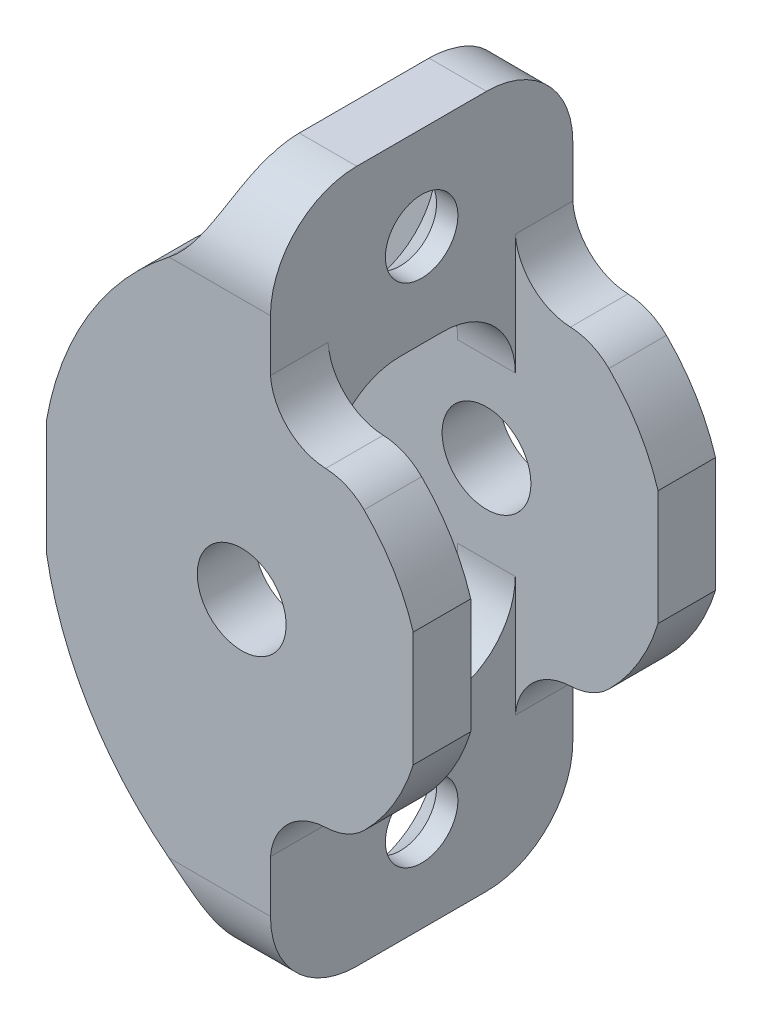
SolidWorks part; units mm, degrees
material "6061-T6 (SS)"
ref_plane "X-Y Datum" through (0, 0, 0) normal (0, 0, 1) x (1, 0, 0)
ref_plane "X-Z Datum" through (0, 0, 0) normal (0, 1, 0) x (1, 0, 0)
ref_plane "Y-Z Datum" through (0, 0, 0) normal (1, 0, 0) x (0, 0, -1)
sketch "Sketch2" plane through (0, 0, 0) normal (1, 0, 0) x (0, 0, -1)
  line L1 (0, 0) -> (33.3756, 0)
  line L2 (0, 0) -> (0, 76.487)
  line L3 (0, 76.487) -> (33.3756, 76.487)
  line L4 (33.3756, 0) -> (33.3756, 76.487)
  dimension "D1" = 33.3756
  dimension "D2" = 76.487
extrude "Body Extrude" add sketch "Sketch2" along normal mid plane 6.35
sketch "Sketch3" plane through (0, 0, 0) normal (0, 0, 1) x (1, 0, 0)
  line L1 (18.9361, 44.5935) -> (18.9361, 31.8935)
  line L2 (-21.5568, 44.5935) -> (-21.5568, 31.8935)
  line L5 (0, 0) -> (0, -50000) construction
  line L6 (3.175, 38.2435) -> (-21.5568, 38.2435) construction
  line L7 (3.175, 76.487) -> (3.175, 0) construction
  line L8 (-3.175, 76.487) -> (-3.175, 0) construction
  line L9 (-3.175, 6.35) -> (3.175, 14.224)
  line L10 (3.175, 0) -> (-3.175, 0) construction
  line L11 (-3.175, 70.137) -> (3.175, 62.263)
  arc A8 (3.175, 14.224) -> (9.271, 21.082) centre (9.5043, 14.7363) cw
  arc A9 (9.271, 21.082) -> (13.5113, 22.9211) centre (9.0377, 27.4277) ccw
  arc A10 (13.5113, 22.9211) -> (18.9361, 31.8935) centre (-1.699, 38.2435) ccw
  arc A11 (-3.175, 6.35) -> (-21.5568, 31.8935) centre (14.2058, 38.2435) cw
  arc A12 (9.271, 55.405) -> (13.5113, 53.5659) centre (9.0377, 49.0593) cw
  arc A13 (3.175, 62.263) -> (9.271, 55.405) centre (9.5043, 61.7507) ccw
  arc A14 (18.9361, 44.5935) -> (13.5113, 53.5659) centre (-1.699, 38.2435) ccw
  arc A15 (-21.5568, 44.5935) -> (-3.175, 70.137) centre (14.2058, 38.2435) cw
  point P3 (0, 0)
  point P6 (3.175, 38.2435)
  point P9 (-3.175, 38.2435)
  point P23 (13.5113, 53.5659)
  point P29 (-3.175, 70.137)
  dimension "D1" = 6.35
  dimension "D5" = 21.082
  dimension "D7" = 21.59
  dimension "D8" = 36.322
  dimension "D3" = 6.35
  dimension "D6" = 6.35
  dimension "D2" = 14.224
  dimension "D4" = 6.096
  dimension "D9" = 12.7
  dimension "D10" = 12.7
extrude "Round Extrude" add sketch "Sketch3" against normal blind 6.35
ref_plane "Plane1" through (0, 0, -16.6878) normal (0, 0, -1) x (-1, 0, 0)
mirror "Round Extrude Mirrored" about plane through (0, 0, -16.6878) normal (0, 0, -1) of "Round Extrude"
sketch "Sketch5" plane through (3.175, 0, 0) normal (1, 0, 0) x (0, 0, -1)
  line L0 (0, 38.2435) -> (-50000, 38.2435) construction
  line L1 (6.35, 55.405) -> (6.35, 61.2384) construction
  line L3 (16.6878, 76.487) -> (16.6878, 50076.487) construction
  line L4 (33.3756, 76.487) -> (0, 76.487) construction
  line L5 (6.35, 55.9092) -> (27.0256, 55.9092)
  line L6 (6.35, 55.9092) -> (6.35, 20.5778)
  line L7 (6.35, 20.5778) -> (27.0256, 20.5778)
  line L8 (27.0256, 55.9092) -> (27.0256, 20.5778)
  line L9 (27.0256, 21.082) -> (27.0256, 15.2486) construction
  line L10 (33.3756, 31.8935) -> (33.3756, 44.5935) construction
  line L11 (33.3756, 31.8935) -> (33.3756, 44.5935) construction
  point P9 (16.6878, 76.487)
  point P20 (33.3756, 38.2435)
  dimension "D1" = 35.3314
  dimension "D2" = 17.6657
extrude "Rectangle Cut" cut sketch "Sketch5" against normal through all
fillet "Back Edge Fillet" radius 12.7 4 edges at (-3.175, 6.35, -30.2006) (-3.175, 6.35, -3.175) (-3.175, 70.137, -30.2006) (-3.175, 70.137, -3.175)
fillet "Outer Fillet" radius 9.525 4 edges at (0, 0, -33.3756) (0, 0, 0) (0, 76.487, -33.3756) (0, 76.487, 0)
fillet "Inner Fillet" radius 7.9375 4 edges at (0, 55.9092, -27.0256) (0, 55.9092, -6.35) (0, 20.5778, -6.35) (0, 20.5778, -27.0256)
sketch "Hole Reference Sketch" plane through (0, 0, 0) normal (1, 0, 0) x (0, 0, -1)
  line L0 (0, 38.2435) -> (50000, 38.2435) construction
  line L2 (16.6878, 76.487) -> (16.6878, -49923.513) construction
  line L3 (23.8506, 76.487) -> (9.525, 76.487) construction
  line L4 (9.525, 0) -> (23.8506, 0) construction
  line L5 (33.3756, 31.8935) -> (33.3756, 44.5935) construction
  line L6 (33.3756, 31.8935) -> (33.3756, 44.5935) construction
  point P9 (16.6878, 76.487)
  point P10 (16.6878, 10.287)
  point P13 (16.6878, 66.2)
  point P16 (33.3756, 38.2435)
  dimension "D1" = 10.287
hole_wizard "CSK for M8 Cross Countersunk Head Screw1" positions "Sketch7" profile "Sketch8" countersink size "M8" standard "AS"
sketch "Sketch7" plane through (-3.175, 0, 0) normal (-1, 0, 0) x (0, 0, 1)
  point P0 (-16.6878, 66.2)
  point P3 (-16.6878, 10.287)
  point P6 (0, 0)
  point P7 (0, 0)
sketch "Sketch8" plane through (-3.175, 66.2, -16.6878) normal (0, 1, 0) x (0, 0, 1)
  line L0 (0, 0) -> (0, 33.782)
  line L1 (0, 33.782) -> (4, 33.782)
  line L2 (4, 33.782) -> (4, 4)
  line L3 (4, 4) -> (8, 0)
  line L5 (8, 0) -> (0, 0)
  line L6 (-4, 4) -> (-8, 0) construction
  line L10 (0, 33.782) -> (-4, 33.782) construction
  line L11 (0, -6.35) -> (0, 107.95) construction
  dimension "Hole Dia." = 8
  dimension "Hole Depth" = 33.782
  dimension "Near C'Sink Dia." = 16
  dimension "Near C'Sink Angle" = 90
  dimension "Drill Angle" = 180
sketch "Sketch9" plane through (0, 0, 0) normal (0, 0, 1) x (1, 0, 0)
  line L0 (0, 200076.487) -> (0, -249923.513) construction
  line L1 (-22.1162, 38.2435) -> (49977.8838, 38.2435) construction
  line L2 (-21.5568, 44.5935) -> (-21.5568, 31.8935) construction
  line L3 (-21.5568, 44.5935) -> (-21.5568, 31.8935) construction
  circle A0 centre (0, 38.2435) radius 4.9022
  point P12 (-21.5568, 38.2435)
  point P13 (-17.408, 98.054)
  point P14 (13.5067, 73.8389)
  dimension "D1" = 9.8044
extrude "Vertical Holes" cut sketch "Sketch9" against normal through all both and the other way through all
sketch "Side Contour Sketch" plane through (-3.175, 0, 0) normal (-1, 0, 0) x (0, 0, 1)
  line L3 (-33.3756, 9.5585) -> (-33.3756, 9.525) construction
  line L4 (-33.3756, 9.5585) -> (-33.3756, 9.525) construction
  line L5 (-9.525, 0) -> (-23.8506, 0) construction
  line L7 (-23.8506, 76.487) -> (-9.525, 76.487) construction
  line L11 (-33.3756, 9.5585) -> (-33.3756, 9.525)
  line L12 (-33.3756, 9.5585) -> (-33.3756, 9.525)
  line L13 (-9.525, 0) -> (-23.8506, 0)
  line L15 (-23.8506, 76.487) -> (-9.525, 76.487)
  line L16 (0, 9.5585) -> (0, 31.8935) construction
  line L17 (-33.3756, 9.5585) -> (-33.3756, 9.525)
  line L20 (0, 44.5935) -> (0, 31.8935) construction
  line L21 (0, 44.5935) -> (0, 66.9285) construction
  line L22 (-33.3756, 66.9285) -> (-33.3756, 44.5935) construction
  line L23 (-33.3756, 31.8935) -> (-33.3756, 44.5935) construction
  line L24 (-33.3756, 31.8935) -> (-33.3756, 9.5585) construction
  line L25 (0, 9.5585) -> (0, 31.8935)
  line L26 (0, 44.5935) -> (0, 31.8935)
  line L27 (0, 44.5935) -> (0, 66.9285)
  line L28 (-33.3756, 66.9285) -> (-33.3756, 44.5935)
  line L29 (-33.3756, 31.8935) -> (-33.3756, 44.5935)
  line L30 (-33.3756, 31.8935) -> (-33.3756, 9.5585)
  line L31 (0, 9.525) -> (0, 9.5585) construction
  line L32 (0, 9.525) -> (0, 9.5585)
  line L33 (-33.3756, 66.962) -> (-33.3756, 66.9285) construction
  line L34 (0, 66.9285) -> (0, 66.962) construction
  line L35 (-33.3756, 66.962) -> (-33.3756, 66.9285)
  line L36 (0, 66.9285) -> (0, 66.962)
  arc A0 (-6.35, 75.9423) -> (-9.525, 76.487) centre (-9.525, 66.962) ccw construction
  arc A2 (-6.35, 0.5447) -> (0, 9.525) centre (-9.525, 9.525) ccw construction
  arc A3 (-9.525, 0) -> (-6.35, 0.5447) centre (-9.525, 9.525) ccw construction
  arc A4 (-27.0256, 0.5447) -> (-23.8506, 0) centre (-23.8506, 9.525) ccw construction
  arc A5 (-33.3756, 9.525) -> (-27.0256, 0.5447) centre (-23.8506, 9.525) ccw construction
  arc A7 (-23.8506, 76.487) -> (-27.0256, 75.9423) centre (-23.8506, 66.962) ccw construction
  arc A8 (-6.35, 75.9423) -> (-9.525, 76.487) centre (-9.525, 66.962) ccw
  arc A10 (-6.35, 0.5447) -> (0, 9.525) centre (-9.525, 9.525) ccw
  arc A11 (-9.525, 0) -> (-6.35, 0.5447) centre (-9.525, 9.525) ccw
  arc A12 (-27.0256, 0.5447) -> (-23.8506, 0) centre (-23.8506, 9.525) ccw
  arc A13 (-33.3756, 9.525) -> (-27.0256, 0.5447) centre (-23.8506, 9.525) ccw
  arc A15 (-23.8506, 76.487) -> (-27.0256, 75.9423) centre (-23.8506, 66.962) ccw
  arc A20 (-27.0256, 75.9423) -> (-33.3756, 66.962) centre (-23.8506, 66.962) ccw construction
  arc A21 (0, 66.962) -> (-6.35, 75.9423) centre (-9.525, 66.962) ccw construction
  arc A22 (-27.0256, 75.9423) -> (-33.3756, 66.962) centre (-23.8506, 66.962) ccw
  arc A23 (0, 66.962) -> (-6.35, 75.9423) centre (-9.525, 66.962) ccw
sketch "Slot Sketch" plane through (-3.175, 0, 0) normal (-1, 0, 0) x (0, 0, 1)
  line L0 (-23.8506, 76.487) -> (-9.525, 76.487) construction
  line L1 (-27.0256, 0) -> (-6.35, 0)
  line L2 (-27.0256, 0) -> (-27.0256, 76.487)
  line L3 (-27.0256, 76.487) -> (-6.35, 76.487)
  line L4 (-6.35, 0) -> (-6.35, 76.487)
  line L7 (-27.0256, 47.9717) -> (-27.0256, 75.9423) construction
  dimension "D1" = 20.6756
  dimension "D2" = 76.487
sketch "Hole Contour" plane through (-3.175, 0, 0) normal (-1, 0, 0) x (0, 0, 1)
  line L0 (-27.0256, 0) -> (-27.0256, 76.487) construction
  line L1 (-14.2875, 55.9092) -> (-19.0881, 55.9092) construction
  line L2 (-6.35, 0) -> (-6.35, 76.487) construction
  line L3 (-19.0881, 20.5778) -> (-14.2875, 20.5778) construction
  line L4 (-27.0256, 28.5153) -> (-27.0256, 47.9717)
  line L5 (-14.2875, 55.9092) -> (-19.0881, 55.9092)
  line L6 (-6.35, 28.5153) -> (-6.35, 47.9717)
  line L7 (-19.0881, 20.5778) -> (-14.2875, 20.5778)
  arc A0 (-19.0881, 55.9092) -> (-27.0256, 47.9717) centre (-19.0881, 47.9717) ccw construction
  arc A1 (-6.35, 47.9717) -> (-14.2875, 55.9092) centre (-14.2875, 47.9717) ccw construction
  arc A2 (-14.2875, 20.5778) -> (-6.35, 28.5153) centre (-14.2875, 28.5153) ccw construction
  arc A3 (-27.0256, 28.5153) -> (-19.0881, 20.5778) centre (-19.0881, 28.5153) ccw construction
  arc A4 (-19.0881, 55.9092) -> (-27.0256, 47.9717) centre (-19.0881, 47.9717) ccw
  arc A5 (-6.35, 47.9717) -> (-14.2875, 55.9092) centre (-14.2875, 47.9717) ccw
  arc A6 (-14.2875, 20.5778) -> (-6.35, 28.5153) centre (-14.2875, 28.5153) ccw
  arc A7 (-27.0256, 28.5153) -> (-19.0881, 20.5778) centre (-19.0881, 28.5153) ccw
sketch "Top Contour Sketch" plane through (0, 0, 0) normal (0, 0, 1) x (1, 0, 0)
  line L0 (-3.207, 75.9423) -> (-3.175, 75.9423) construction
  line L1 (-3.175, 76.487) -> (-3.175, 75.9423) construction
  line L2 (-3.175, 76.487) -> (3.175, 76.487) construction
  line L3 (3.175, 66.962) -> (3.175, 76.487) construction
  line L4 (3.175, 66.962) -> (3.175, 61.2384) construction
  line L5 (3.175, 15.2486) -> (3.175, 9.525) construction
  line L6 (3.175, 0) -> (3.175, 9.525) construction
  line L7 (3.175, 0) -> (-3.175, 0) construction
  line L8 (-3.175, 0.5447) -> (-3.175, 0) construction
  line L9 (-3.175, 0.5447) -> (-3.207, 0.5447) construction
  line L10 (-3.207, 75.9423) -> (-3.175, 75.9423)
  line L11 (-3.175, 76.487) -> (-3.175, 75.9423)
  line L12 (-3.175, 76.487) -> (3.175, 76.487)
  line L13 (3.175, 66.962) -> (3.175, 76.487)
  line L14 (3.175, 66.962) -> (3.175, 61.2384)
  line L15 (3.175, 15.2486) -> (3.175, 9.525)
  line L16 (3.175, 0) -> (3.175, 9.525)
  line L17 (3.175, 0) -> (-3.175, 0)
  line L18 (-3.175, 0.5447) -> (-3.175, 0)
  line L19 (-3.175, 0.5447) -> (-3.207, 0.5447)
  line L20 (-21.5568, 44.5935) -> (-21.5568, 31.8935) construction
  line L21 (18.9361, 31.8935) -> (18.9361, 44.5935) construction
  line L22 (-21.5568, 44.5935) -> (-21.5568, 31.8935)
  line L23 (18.9361, 31.8935) -> (18.9361, 44.5935)
  arc A2 (3.175, 61.2384) -> (9.271, 55.405) centre (9.5043, 61.7507) ccw construction
  arc A11 (3.175, 61.2384) -> (9.271, 55.405) centre (9.5043, 61.7507) ccw
  arc A18 (-3.207, 0.5447) -> (-8.0326, 9.525) centre (-15.8663, -0.4712) ccw construction
  arc A19 (-3.207, 0.5447) -> (-8.0326, 9.525) centre (-15.8663, -0.4712) ccw
  arc A20 (-8.0326, 66.962) -> (-3.207, 75.9423) centre (-15.8663, 76.9582) ccw construction
  arc A21 (-8.0756, 66.9285) -> (-21.5568, 44.5935) centre (14.2058, 38.2435) ccw construction
  arc A22 (-21.5568, 31.8935) -> (-8.0756, 9.5585) centre (14.2058, 38.2435) ccw construction
  arc A23 (9.271, 21.082) -> (3.175, 15.2486) centre (9.5043, 14.7363) ccw construction
  arc A24 (9.271, 21.082) -> (13.5113, 22.9211) centre (9.0377, 27.4277) ccw construction
  arc A25 (13.5113, 22.9211) -> (18.9361, 31.8935) centre (-1.699, 38.2435) ccw construction
  arc A26 (18.9361, 44.5935) -> (13.5113, 53.5659) centre (-1.699, 38.2435) ccw construction
  arc A27 (13.5113, 53.5659) -> (9.271, 55.405) centre (9.0377, 49.0593) ccw construction
  arc A28 (-8.0326, 66.962) -> (-3.207, 75.9423) centre (-15.8663, 76.9582) ccw
  arc A29 (-8.0756, 66.9285) -> (-21.5568, 44.5935) centre (14.2058, 38.2435) ccw
  arc A30 (-21.5568, 31.8935) -> (-8.0756, 9.5585) centre (14.2058, 38.2435) ccw
  arc A31 (9.271, 21.082) -> (3.175, 15.2486) centre (9.5043, 14.7363) ccw
  arc A32 (9.271, 21.082) -> (13.5113, 22.9211) centre (9.0377, 27.4277) ccw
  arc A33 (13.5113, 22.9211) -> (18.9361, 31.8935) centre (-1.699, 38.2435) ccw
  arc A34 (18.9361, 44.5935) -> (13.5113, 53.5659) centre (-1.699, 38.2435) ccw
  arc A35 (13.5113, 53.5659) -> (9.271, 55.405) centre (9.0377, 49.0593) ccw
  arc A36 (-8.0326, 9.525) -> (-8.0756, 9.5585) centre (-15.8663, -0.4712) ccw construction
  arc A37 (-8.0326, 9.525) -> (-8.0756, 9.5585) centre (-15.8663, -0.4712) ccw
  arc A38 (-8.0756, 66.9285) -> (-8.0326, 66.962) centre (-15.8663, 76.9582) ccw construction
  arc A39 (-8.0756, 66.9285) -> (-8.0326, 66.962) centre (-15.8663, 76.9582) ccw
sketch "Top/Bottom Reference Rect" plane through (0, 0, 0) normal (0, 0, 1) x (1, 0, 0)
  line L1 (-22.1162, 76.4786) -> (22.1162, 76.4786)
  line L2 (-22.1162, 76.4786) -> (-22.1162, 0.0085)
  line L3 (-22.1162, 0.0085) -> (22.1162, 0.0085)
  line L4 (22.1162, 76.4786) -> (22.1162, 0.0085)
  line L5 (-22.1162, 76.4786) -> (22.1162, 0.0085) construction
  line L6 (-22.1162, 0.0085) -> (22.1162, 76.4786) construction
  line L8 (-8.0326, 9.525) -> (3.175, 9.525) construction
  arc A0 (-21.5568, 31.8935) -> (-8.0756, 9.5585) centre (14.2058, 38.2435) ccw construction
  point P0 (0, 38.2435)
  dimension "D1" = 66.9536
sketch "Front Ref" plane through (3.175, 0, 0) normal (1, 0, 0) x (0, 0, -1)
  line L0 (33.3756, 22.9211) -> (33.3756, 31.8935) construction
  line L1 (0, 0) -> (33.3756, 0)
  line L2 (0, 0) -> (0, 76.487)
  line L3 (0, 76.487) -> (33.3756, 76.487)
  line L4 (33.3756, 0) -> (33.3756, 76.487)
  line L5 (23.8506, 76.487) -> (9.525, 76.487) construction
sketch "Back Ref" plane through (-3.175, 0, 0) normal (-1, 0, 0) x (0, 0, 1)
  line L1 (0, 0) -> (-39.7256, 0)
  line L2 (0, 0) -> (0, 76.487)
  line L3 (0, 76.487) -> (-39.7256, 76.487)
  line L4 (-39.7256, 0) -> (-39.7256, 76.487)
  line L5 (-23.8506, 76.487) -> (-9.525, 76.487) construction
  line L7 (-9.525, 0) -> (-23.8506, 0) construction
  line L9 (0, 9.5585) -> (0, 31.8935) construction
  line L12 (-33.3756, 31.8935) -> (-33.3756, 9.5585) construction
  dimension "D1" = 6.35
sketch "Front Slot 3D Adaptive Boundary" plane through (3.175, 0, 0) normal (1, 0, 0) x (0, 0, -1)
  line L1 (6.35, 61.2384) -> (27.0256, 61.2384)
  line L2 (6.35, 61.2384) -> (6.35, 15.2486)
  line L3 (6.35, 15.2486) -> (27.0256, 15.2486)
  line L4 (27.0256, 61.2384) -> (27.0256, 15.2486)
sketch "Fillet 3D Adaptive Boundary" plane through (0, 0, 0) normal (0, 0, 1) x (1, 0, 0)
  line L0 (3.175, 66.962) -> (3.175, 76.487) construction
  line L1 (3.175, 76.995) -> (-3.175, 76.995)
  line L2 (3.175, 76.995) -> (3.175, -0.508)
  line L3 (3.175, -0.508) -> (-3.175, -0.508)
  line L4 (-3.175, 76.995) -> (-3.175, -0.508)
  line L5 (-3.175, 76.487) -> (3.175, 76.487) construction
  line L6 (3.175, 0) -> (-3.175, 0) construction
  line L8 (-3.175, 76.487) -> (-3.175, 75.9423) construction
  dimension "D1" = 0.508
  dimension "D2" = 0.508
sketch "Top Centerpoint" plane through (0, 0, -33.3756) normal (0, 0, -1) x (-1, 0, 0)
  line L0 (-18.9361, 38.2435) -> (21.5568, 38.2435) construction
  line L3 (-18.9361, 31.8935) -> (-18.9361, 44.5935) construction
  line L4 (21.5568, 44.5935) -> (21.5568, 31.8935) construction
  point P8 (0, 0)
  point P14 (1.3104, 38.2435)
